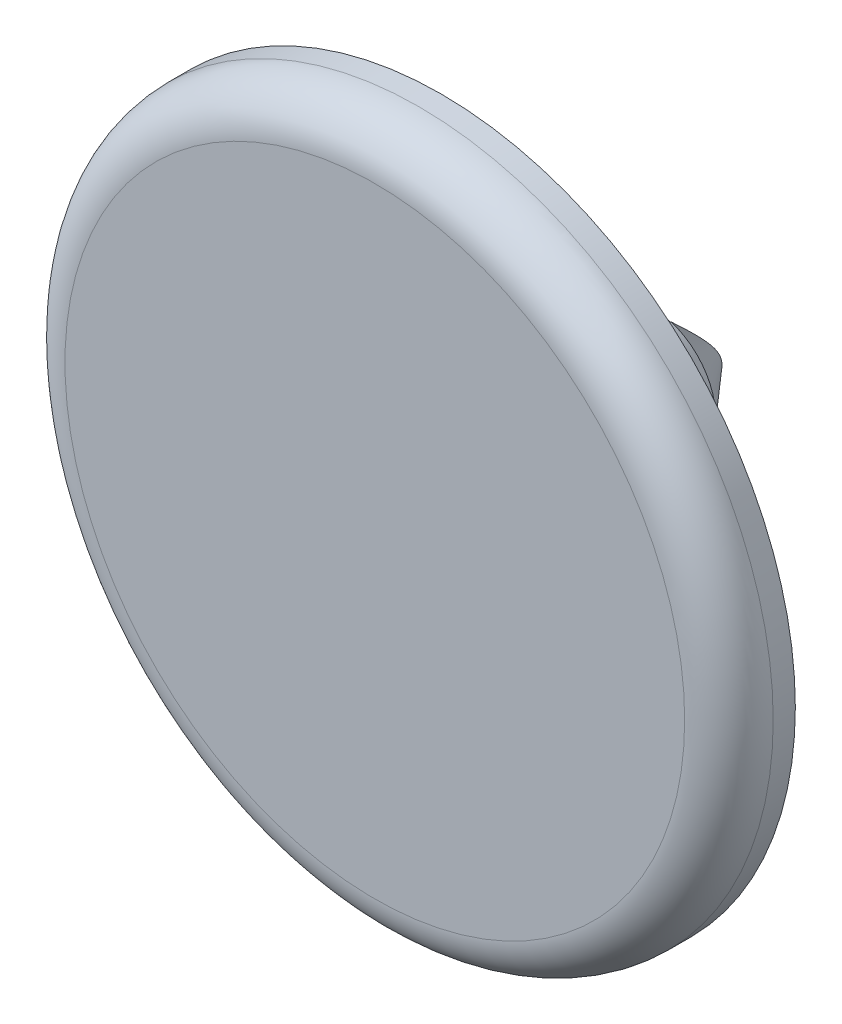
SolidWorks part; units mm, degrees
ref_plane "Спереди" through (0, 0, 0) normal (0, 0, 1) x (1, 0, 0)
ref_plane "Сверху" through (0, 0, 0) normal (0, 1, 0) x (1, 0, 0)
ref_plane "Справа" through (0, 0, 0) normal (1, 0, 0) x (0, 0, -1)
sketch "Эскиз1" plane through (0, 0, 0) normal (0, 0, 1) x (1, 0, 0)
  circle A0 centre (0, 0) radius 8
  dimension "D1" = 16
extrude "Бобышка-Вытянуть1" add sketch "Эскиз1" along normal blind 1.5
sketch "Эскиз2" plane through (0, 0, 0) normal (0, 0, -1) x (-1, 0, 0)
  circle A0 centre (0, 0) radius 1.55
  dimension "D1" = 3.1
extrude "Бобышка-Вытянуть2" add sketch "Эскиз2" along normal blind 3.4
fillet "Скругление1" radius 1 1 edges at (8, 0, 1.5)
sketch "Эскиз4" plane through (0, 0, -3.4) normal (0, 0, -1) x (-1, 0, 0)
  circle A0 centre (0, 0) radius 1.75
  dimension "D1" = 3.5
extrude "Бобышка-Вытянуть3" add sketch "Эскиз4" along normal blind 3
chamfer "Фаска4" distance 2 angle 41 1 edges at (-1.75, 0, -6.4) first distance on face at (-1.75, 0, -6.4)
fillet "Скругление3" radius 0.3 1 edges at (-1.55, 0, 0)
sketch "Эскиз5" plane through (0, 0, -6.4) normal (0, 0, -1) x (-1, 0, 0)
  line L1 (-0.5, 2.1701) -> (0.5, 2.1701)
  line L2 (-0.5, 2.1701) -> (-0.5, -2.1701)
  line L3 (-0.5, -2.1701) -> (0.5, -2.1701)
  line L4 (0.5, 2.1701) -> (0.5, -2.1701)
  line L5 (-0.5, 2.1701) -> (0.5, -2.1701) construction
  line L6 (-0.5, -2.1701) -> (0.5, 2.1701) construction
  point P0 (0, 0)
  dimension "D1" = 1
extrude "Вырез-Вытянуть2" cut sketch "Эскиз5" against normal blind 5.7 draft 3
chamfer "Фаска5" distance 0.5 angle 20 1 edges at (1.75, 0, -4.4) first distance on face at (1.1111, -0.008, -5.1348)
chamfer "Фаска6" distance 0.5 angle 20 1 edges at (-1.75, 0, -4.4) first distance on face at (-1.1111, 0.008, -5.1348)
